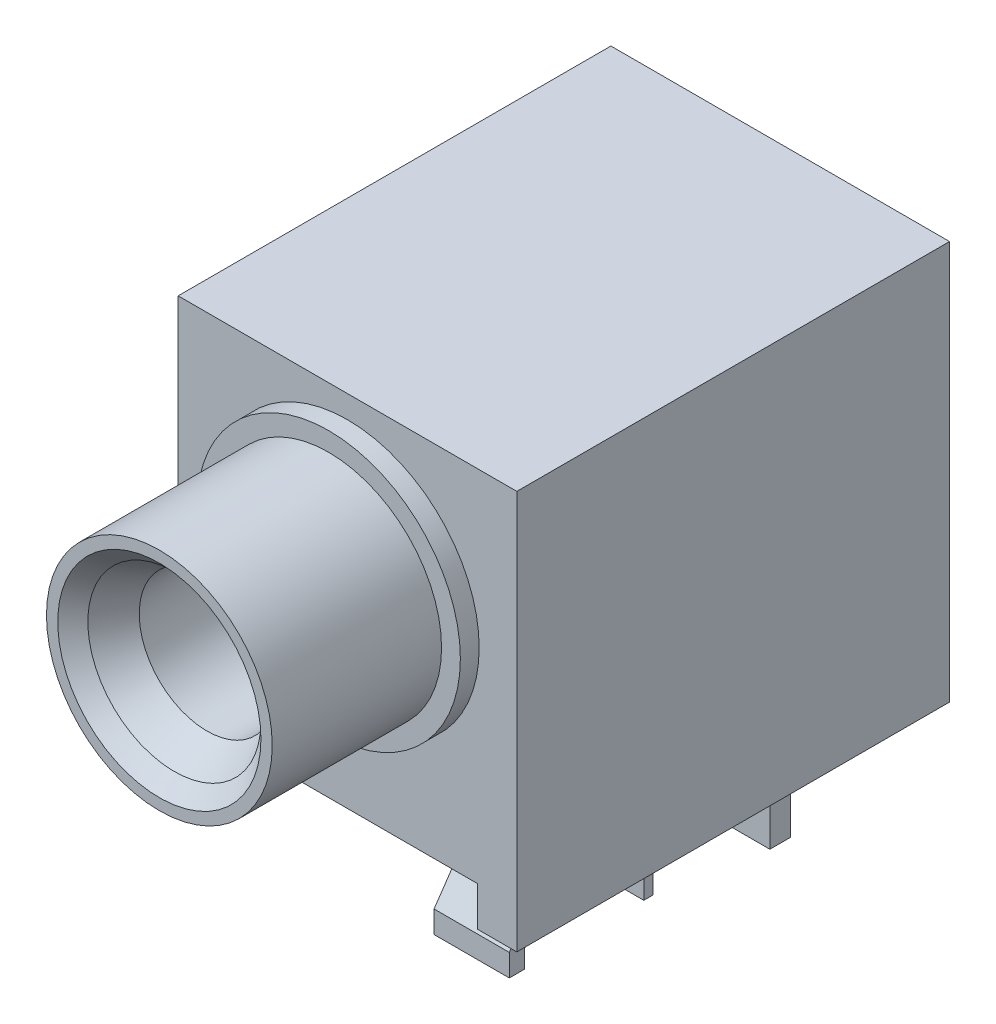
SolidWorks part; units mm, degrees
ref_plane "Front Plane" through (0, 0, 0) normal (0, 0, 1) x (1, 0, 0)
ref_plane "Top Plane" through (0, 0, 0) normal (0, 1, 0) x (1, 0, 0)
ref_plane "Right Plane" through (0, 0, 0) normal (1, 0, 0) x (0, 0, -1)
sketch "Sketch1" plane through (0, 0, 0) normal (0, 0, 1) x (1, 0, 0)
  line L0 (90.3126, 311.66) -> (451.5631, 311.66) construction
  line L1 (-4.5, 10.6) -> (4.5, 10.6)
  line L2 (-4.5, 10.6) -> (-4.5, 0)
  line L3 (-4.5, 0) -> (-3.45, 0)
  line L4 (-3.45, 0) -> (-3.45, 1.05)
  line L5 (-3.45, 1.05) -> (3.45, 1.05)
  line L6 (0, 10.6) -> (0, 1.05) construction
  line L7 (3.45, 0) -> (3.45, 1.05)
  line L8 (4.5, 0) -> (3.45, 0)
  line L9 (4.5, 10.6) -> (4.5, 0)
  point P9 (0, 1.05)
  dimension "D1" = 4.5
  dimension "D2" = 10.6
  dimension "D3" = 1.05
extrude "Boss-Extrude1" add sketch "Sketch1" against normal blind 11.5
sketch "Sketch2" plane through (0, 0, 0) normal (0, 0, 1) x (1, 0, 0)
  line L0 (-4.5, 0) -> (-3.45, 0) construction
  circle A0 centre (0, 6.5) radius 3.5
  dimension "D1" = 7
  dimension "D2" = 6.5
extrude "Boss-Extrude2" add sketch "Sketch2" along normal blind 0.5 separate body
sketch "Sketch3" plane through (0, 0, 0.5) normal (0, 0, 1) x (1, 0, 0)
  circle A0 centre (0, 6.5) radius 3
  circle A1 centre (0, 6.5) radius 3.5 construction
  dimension "D1" = 6
extrude "Boss-Extrude3" add sketch "Sketch3" along normal blind 4.5
ref_axis "Axis1" through (0, 6.5, 5) along (0, 0, -1)
ref_plane "Plane1" through (0, 6.5, 0) normal (0, 1, 0) x (1, 0, 0)
sketch "Sketch4" plane through (0, 6.5, 0) normal (0, 1, 0) x (1, 0, 0)
  line L0 (0, 0) -> (1.8, 0)
  line L1 (1.8, 0) -> (1.8, -3.734)
  line L3 (2.7, -5) -> (0, -5)
  line L4 (0, -5) -> (0, 0)
  line L5 (2.7, -5) -> (2.3, -4.6)
  line L6 (-3, -5) -> (3, -5) construction
  line L7 (2.3, -4.6) -> (1.8, -3.734)
  dimension "D1" = 1.8
  dimension "D2" = 2.7
  dimension "D3" = 45
  dimension "D4" = 60
  dimension "D5" = 0.4
  dimension "D6" = 0.5
revolve "Cut-Revolve1" cut sketch "Sketch4" angle 360 about L4
sketch "Sketch5" plane through (0, 0, 0) normal (1, 0, 0) x (0, 0, -1)
  line L0 (134.9814, 404.45) -> (710.3148, 404.45) construction
  line L1 (3.3, 1.05) -> (3.3, -1.2553)
  line L2 (11.5, 1.05) -> (0, 1.05) construction
  line L3 (3.3, -1.2553) -> (3.8704, -2.5818)
  line L4 (3.8704, -2.5818) -> (3.3, -3.4102)
  line L5 (3.3, -3.4102) -> (3.3, -4)
  line L6 (3.7, 1.05) -> (3.7, -1.173)
  line L7 (3.7, -1.173) -> (4.3251, -2.6267)
  line L8 (4.3251, -2.6267) -> (3.7, -3.5346)
  line L9 (3.7, -3.5346) -> (3.7, -4)
  line L10 (3.3, 1.05) -> (3.7, 1.05)
  line L11 (3.3, -4) -> (3.7, -4)
  line L12 (11.5, 0) -> (0, 0) construction
  line L14 (6.875, 1.05) -> (7.125, 1.05)
  line L15 (6.875, 1.05) -> (6.875, -4)
  line L16 (6.875, -4) -> (7.125, -4)
  line L17 (7.125, 1.05) -> (7.125, -4)
  line L18 (10.225, 1.05) -> (10.775, 1.05)
  line L19 (10.225, 1.05) -> (10.225, -4.5)
  line L20 (10.225, -4.5) -> (10.775, -4.5)
  line L21 (10.775, 1.05) -> (10.775, -4.5)
  point P21 (3.5, -4)
  point P23 (7, -4)
  point P28 (10.5, -4.5)
  dimension "D1" = 0.4
  dimension "D2" = 4
  dimension "D3" = 0.25
  dimension "D4" = 3.5
  dimension "D5" = 3.5
  dimension "D6" = 4.5
  dimension "D7" = 0.55
  dimension "D8" = 3.5
extrude "Boss-Extrude4" add sketch "Sketch5" along normal mid plane 2 separate body
